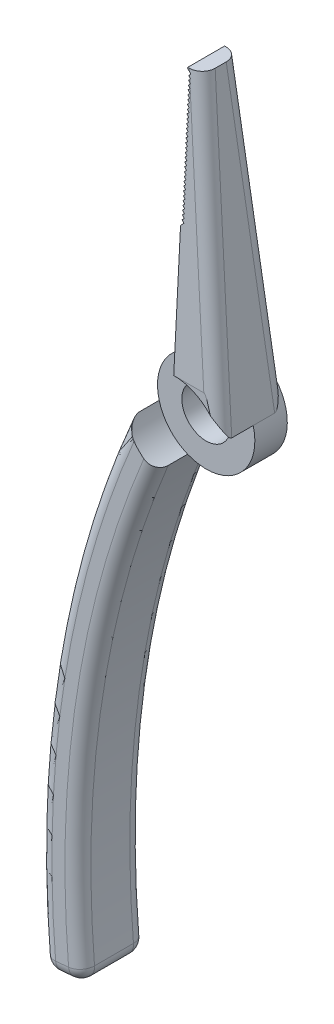
SolidWorks part; units mm, degrees
ref_plane "Front Plane" through (0, 0, 0) normal (0, 0, 1) x (1, 0, 0)
ref_plane "Top Plane" through (0, 0, 0) normal (0, 1, 0) x (1, 0, 0)
ref_plane "Right Plane" through (0, 0, 0) normal (1, 0, 0) x (0, 0, -1)
sketch "Sketch2" plane through (0, 0, 0) normal (0, 0, 1) x (1, 0, 0)
  line L0 (0, 9.525) -> (0, 60.3766)
  line L1 (0, 60.3766) -> (2.8395, 60.3766)
  line L2 (2.8395, 60.3766) -> (9.2004, 2.4653)
  line L3 (0, 0) -> (9.525, 0)
  line L4 (9.2004, 2.4653) -> (9.1996, 2.4653)
  line L5 (9.1996, 2.4653) -> (0, 9.525)
  circle A0 centre (0, 0) radius 9.525
  dimension "D1" = 19.05
  dimension "D2" = 0.0535
  dimension "D3" = 15
extrude "Boss-Extrude2" add sketch "Sketch2" against normal mid plane 12.7 contours A0 | L5 L0 L1 L2 L4
sketch "Sketch3" plane through (0, 0, 6.35) normal (0, 0, 1) x (1, 0, 0)
  line L0 (-9.2004, -2.4653) -> (9.2004, 2.4653) construction
  arc A0 (-9.2004, -2.4653) -> (-25.4, -104.0653) centre (176.8284, -84.218) ccw
  point P6 (0, 0)
  dimension "D2" = 203.2
  dimension "D1" = 101.6
  dimension "D3" = 25.4
extrude "Extrude-Thin1" add sketch "Sketch3" against normal blind 12.7 thin thin type one direction reverse wall 7.62
sketch "Sketch4" plane through (0, 0, 6.35) normal (0, 0, 1) x (1, 0, 0)
  circle A0 centre (0, 0) radius 4.7625
  dimension "D1" = 9.525
extrude "Cut-Extrude1" cut sketch "Sketch4" against normal through all contours A0
extrude "Cut-Extrude3" cut sketch "Sketch2<5>" along normal through all contours A0
sketch "Sketch2<5>" plane through (0, 0, 0) normal (0, 0, 1) x (1, 0, 0) same geometry as "Sketch2"
sketch "Sketch7" plane through (0, 0, 0) normal (-1, 0, 0) x (0, 0, 1)
  line L0 (3.6096, 60.3766) -> (6.35, 9.525)
  line L1 (-6.35, 60.3766) -> (6.35, 60.3766) construction
  dimension "D1" = 6.8534
extrude "Cut-Extrude5" cut sketch "Sketch7" against normal through all and the other way through all
mirror "Mirror1" about plane through (0, 0, 0) normal (0, 0, 1) of "Cut-Extrude5"
fillet "Fillet1" radius 2.54 10 edges at (-17.8164, -103.321, 0) (-21.6082, -103.6931, -6.35) (-25.4, -104.0653, 0) (-21.6082, -103.6931, 6.35) (-16.5845, -55.1839, 6.35) (-16.5845, -55.1839, -6.35) (-23.8369, -52.223, -6.35) (-23.8369, -52.223, 6.35) (5.6322, 34.9508, -4.9798) (5.6322, 34.9508, 4.9798)
sketch "Sketch8" plane through (0, 0, 0) normal (0, 0, 1) x (1, 0, 0)
  line L0 (0, 34.9508) -> (0.6418, 34.9508) construction
  line L1 (0, 9.525) -> (0, 60.3766) construction
  line L2 (0, 34.2896) -> (0.6418, 34.9508)
  line L3 (0.6418, 34.9508) -> (0, 35.612)
  point P5 (0, 35.6074)
  point P7 (0, 35.4146)
  point P8 (0, 34.3937)
  dimension "D1" = 135.852
extrude "Cut-Extrude6" cut sketch "Sketch8" against normal through all and the other way through all
pattern_linear "LPattern1" count 32 spacing 0.7937 along (0, 1, 0) of "Cut-Extrude6"
